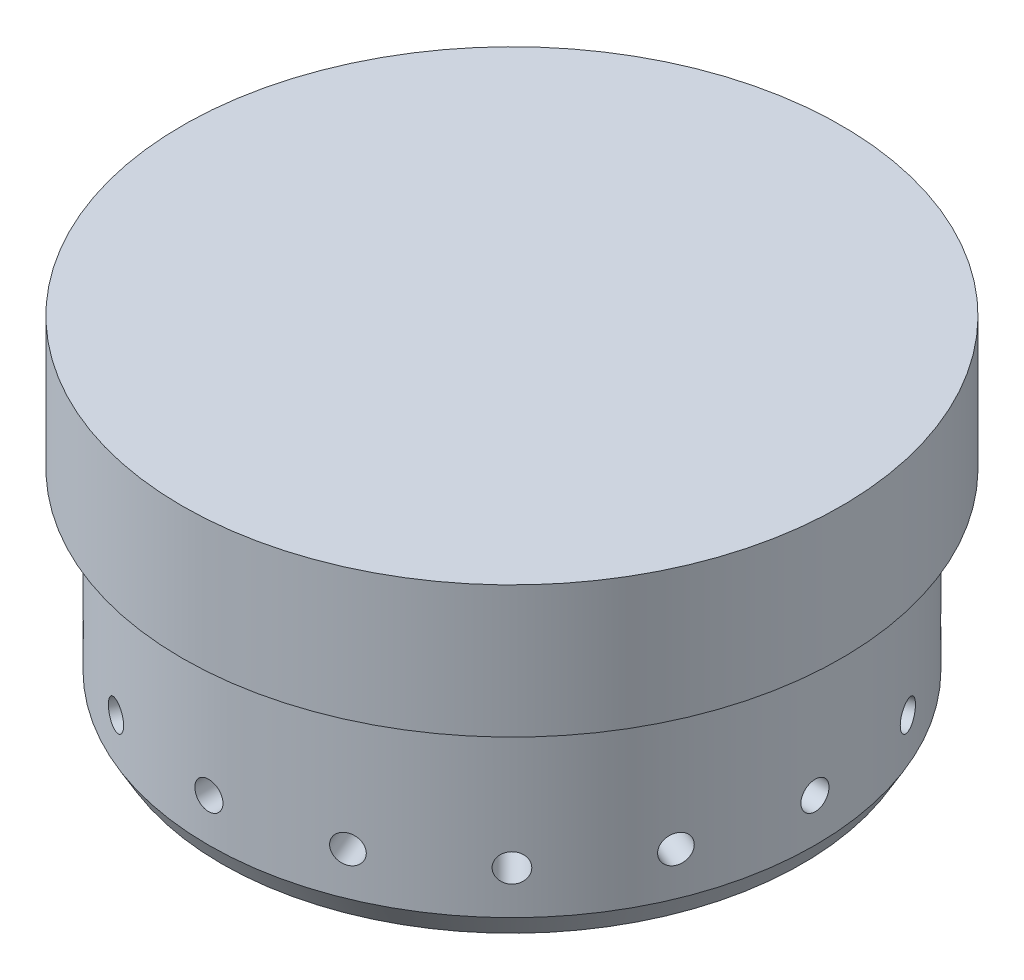
SolidWorks part; units mm, degrees
material "6061-T6 (SS)"
ref_plane "Front Plane" through (0, 0, 0) normal (0, 0, 1) x (1, 0, 0)
ref_plane "Top Plane" through (0, 0, 0) normal (0, 1, 0) x (1, 0, 0)
ref_plane "Right Plane" through (0, 0, 0) normal (1, 0, 0) x (0, 0, -1)
ref_axis "Center Axis" through (0, 0, 0) along (0, 1, 0)
sketch "Sketch1" plane through (0, 0, 0) normal (0, 0, 1) x (1, 0, 0)
  line L0 (0, 0) -> (-58.4454, 0)
  line L1 (-58.4454, 0) -> (-58.4454, 38.1)
  line L2 (-58.4454, 38.1) -> (-63.5, 38.1)
  line L3 (-63.5, 38.1) -> (-63.5, 63.5)
  line L4 (-63.5, 63.5) -> (0, 63.5)
  line L5 (0, 63.5) -> (0, 0)
  dimension "D1" = 58.4454
  dimension "D2" = 63.5
  dimension "D3" = 38.1
revolve "Revolve1" add sketch "Sketch1" angle 360 about L5
ref_plane "Tap Reference Plane" through (0, 0, 58.4454) normal (0, 0, 1) x (1, 0, 0)
sketch "Hole Reference" plane through (0, 0, 58.4454) normal (0, 0, 1) x (1, 0, 0)
  line L0 (0, 0) -> (0, 12.7)
  point P4 (0, 12.7)
hole_wizard "1/4-28 Tap" positions "Sketch11" profile "Sketch13" hole size "1/4-28" standard "ANSI Inch"
sketch "Sketch11" plane through (0, 0, 58.4454) normal (0, 0, 1) x (1, 0, 0)
  point P0 (0, 12.7)
sketch "Sketch13" plane through (0, 12.7, 58.4454) normal (1, 0, 0) x (0, -1, 0)
  line L0 (0, 0) -> (0, 20.6754)
  line L1 (0, 20.6754) -> (2.7051, 19.05)
  line L2 (2.7051, 19.05) -> (2.7051, 0)
  line L5 (2.7051, 0) -> (0, 0)
  line L10 (0, 20.6754) -> (-2.7051, 19.05) construction
  line L11 (0, -6.35) -> (0, 107.95) construction
  dimension "Hole Dia." = 5.4102
  dimension "Hole Depth" = 19.05
  dimension "Drill Angle" = 118
pattern_circular "Tap Pattern" count 16 over 360 about axis through (0, 0, 0) along (0, 1, 0) of "1/4-28 Tap"
chamfer "Chamfer1" distance 2.54 angle 60 1 edges at (0, 0, 58.4454) first distance on face at (0, 0, 58.4454)
